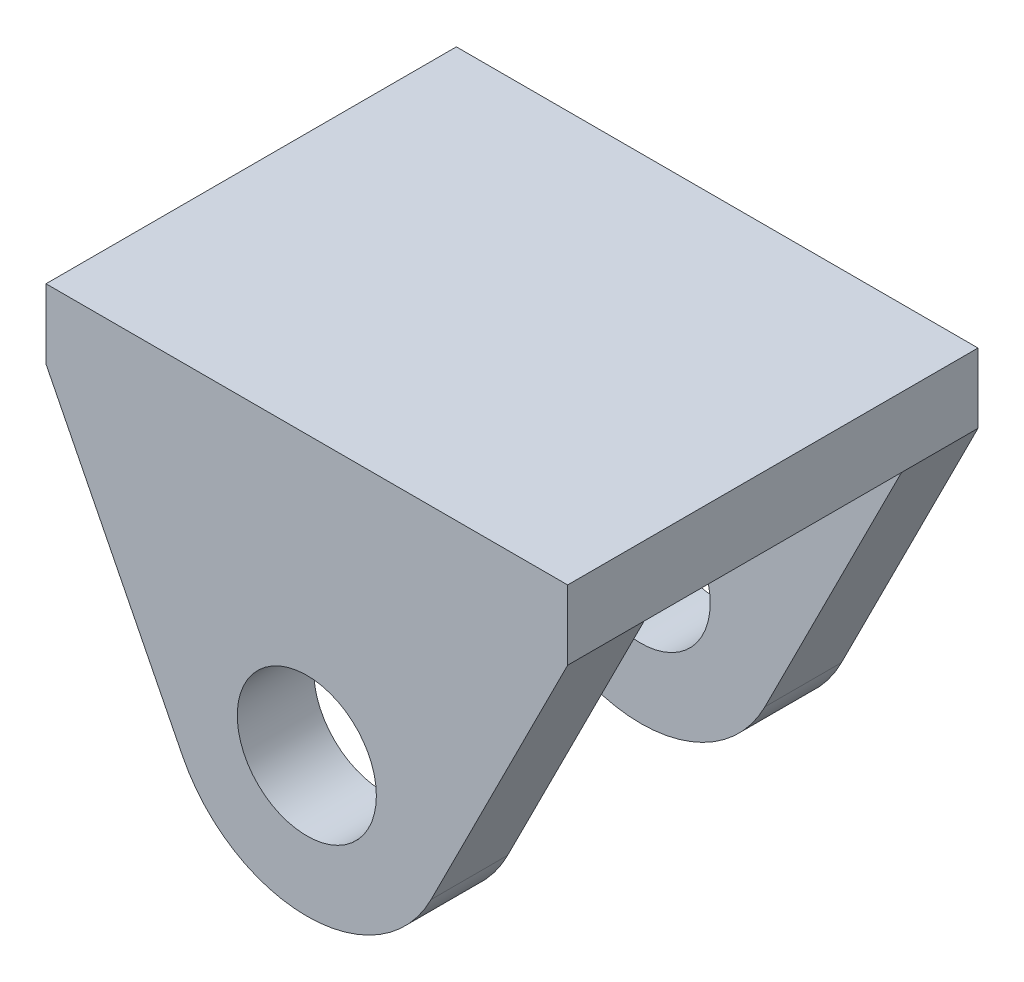
SolidWorks part; units mm, degrees
ref_plane "Front Plane" through (0, 0, 0) normal (0, 0, 1) x (1, 0, 0)
ref_plane "Top Plane" through (0, 0, 0) normal (0, 1, 0) x (1, 0, 0)
ref_plane "Right Plane" through (0, 0, 0) normal (1, 0, 0) x (0, 0, -1)
sketch "Sketch1" plane through (0, 0, 0) normal (0, 0, 1) x (1, 0, 0)
  line L0 (-3, 9.5394) -> (3, 9.5394)
  line L1 (-37.5, 30) -> (37.5, 30)
  line L2 (-17.8629, -8.9953) -> (-37.5, 30)
  line L3 (17.8629, -8.9953) -> (37.5, 30)
  line L4 (-37.5, 30) -> (-37.5, 40)
  line L5 (-37.5, 40) -> (37.5, 40)
  line L6 (37.5, 40) -> (37.5, 30)
  circle A0 centre (0, 0) radius 20
  circle A1 centre (0, 0) radius 10
  dimension "D1" = 40
  dimension "D2" = 20
  dimension "D3" = 6
  dimension "D4" = 30
  dimension "D5" = 75
  dimension "D7" = 10
extrude "Boss-Extrude1" add sketch "Sketch1" against normal blind 11 contours A0 L3 L1 L2 | A0 A1 region at (0, 20.156, 0) region at (-4.4921, 18.908, 0)
extrude "Boss-Extrude2" add sketch "Sketch1<3>" against normal blind 59 contours L6 L5 L4 L1 region at (0, 35, 0)
sketch "Sketch1<3>" plane through (0, 0, 0) normal (0, 0, 1) x (1, 0, 0) same geometry as "Sketch1"
ref_plane "Plane2" through (0, 0, -29.5) normal (0, 0, 1) x (1, 0, 0)
mirror "Mirror2" about plane through (0, 0, -29.5) normal (0, 0, 1) of "Boss-Extrude1"
